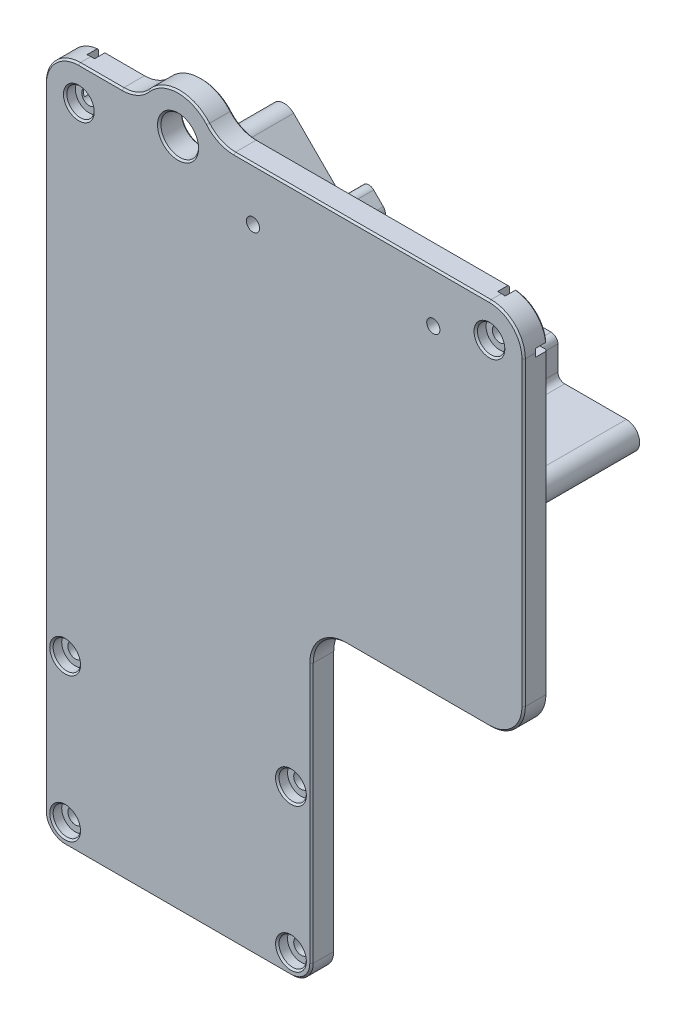
SolidWorks part; units mm, degrees
material "Petg 30% Infill"
ref_plane "Front Plane" through (0, 0, 0) normal (0, 0, 1) x (1, 0, 0)
ref_plane "Top Plane" through (0, 0, 0) normal (0, 1, 0) x (1, 0, 0)
ref_plane "Right Plane" through (0, 0, 0) normal (1, 0, 0) x (0, 0, -1)
sketch "Sketch1" plane through (0, 0, 0) normal (0, 0, 1) x (1, 0, 0)
  line L1 (-29, 200) -> (-16.3172, 200)
  line L2 (-39, 190) -> (-39, 6)
  line L3 (-33, 0) -> (33, 0)
  line L4 (39, 82) -> (39, 6)
  line L5 (101, 190) -> (101, 102)
  line L6 (91, 92) -> (49, 92)
  line L10 (16.3172, 200) -> (91, 200)
  arc A2 (-29, 200) -> (-39, 190) centre (-29, 190) ccw
  arc A5 (49, 92) -> (39, 82) centre (49, 82) ccw
  arc A6 (101, 102) -> (91, 92) centre (91, 102) cw
  arc A7 (91, 200) -> (101, 190) centre (91, 190) cw
  arc A19 (-8.7278, 203.4884) -> (-16.3172, 200) centre (-16.3172, 210) cw
  circle A20 centre (0, 196) radius 5.5
  arc A21 (8.7278, 203.4884) -> (-8.7278, 203.4884) centre (0, 196) ccw
  arc A22 (8.7278, 203.4884) -> (16.3172, 200) centre (16.3172, 210) ccw
  circle A23 centre (-33, 48) radius 2.2
  circle A24 centre (-33, 6) radius 2.2
  circle A25 centre (33, 6) radius 2.2
  circle A26 centre (33, 48) radius 2.2
  arc A27 (-39, 6) -> (-33, 0) centre (-33, 6) ccw
  arc A28 (33, 0) -> (39, 6) centre (33, 6) ccw
  point P4 (0, 0)
  point P70 (10.7819, 200)
  point P80 (-39, 0)
  point P83 (39, 0)
  dimension "D3" = 10
  dimension "D5" = 11
  dimension "D6" = 42
  dimension "D7" = 66
  dimension "D8" = 39
  dimension "D9" = 10
  dimension "D10" = 6
  dimension "D13" = 4.4
  dimension "D1" = 78
  dimension "D2" = 200
  dimension "D4" = 140
  dimension "D12" = 108
  dimension "D14" = 4
extrude "Boss-Extrude1" add sketch "Sketch1" along normal blind 7
sketch "Sketch4" plane through (0, 0, 0) normal (0, 0, -1) x (-1, 0, 0)
  circle A0 centre (29, 190) radius 2.15
  circle A1 centre (-91, 190) radius 2.15
  arc A2 (-91, 200) -> (-101, 190) centre (-91, 190) ccw construction
  dimension "D1" = 4.3
extrude "Cut-Extrude4" cut sketch "Sketch4" against normal up to surface (7 mm away) up to face at (25.25, 123.1865, 7)
sketch "Sketch3" plane through (0, 0, 0) normal (0, 0, -1) x (-1, 0, 0)
  circle A0 centre (-33, 48) radius 4
  circle A1 centre (-33, 6) radius 4
  circle A3 centre (33, 6) radius 4
  circle A4 centre (33, 48) radius 4
  circle A5 centre (-33, 6) radius 2.2 construction
  circle A6 centre (-33, 48) radius 2.2 construction
  circle A7 centre (33, 48) radius 2.2 construction
  circle A8 centre (33, 6) radius 2.2 construction
  circle A9 centre (29, 190) radius 4
  circle A10 centre (-91, 190) radius 4
  dimension "D1" = 8
extrude "countersinks" cut sketch "Sketch3" along normal blind 3 and the other way through all from surface starting at face at (-31.15, 190, 7)
sketch "Sketch7" plane through (0, 0, 0) normal (0, 0, -1) x (-1, 0, 0)
  line L1 (-4.4745, 203.75) -> (-8.9489, 196)
  line L2 (-8.9489, 196) -> (-4.4745, 188.25)
  line L3 (-4.4745, 188.25) -> (4.4745, 188.25)
  line L4 (4.4745, 188.25) -> (8.9489, 196)
  line L5 (8.9489, 196) -> (4.4745, 203.75)
  line L6 (4.4745, 203.75) -> (-4.4745, 203.75)
  circle A0 centre (0, 196) radius 7.75 construction
  arc A1 (8.7278, 203.4884) -> (-8.7278, 203.4884) centre (0, 196) ccw construction
  dimension "D1" = 15.5
extrude "Cut-Extrude7" [suppressed] cut sketch "Sketch7" along normal blind 5.5 from surface starting at face at (87, 190, 7)
chamfer "Chamfer1" distance 0.5 angle 45 46 edges at (35.2, 48, 0) (-30.8, 6, 0) (53.6586, 200, 0) (12.1408, 200.9138, 0) (0, 207.5, 0) (-12.1408, 200.9138, 0) (-22.6586, 200, 0) (-36.0711, 197.0711, 0) (-39, 98, 0) (-37.2426, 1.7574, 0) (0, 0, 0) (37.2426, 1.7574, 0) (39, 44, 0) (41.9289, 89.0711, 0) (70, 92, 0) (98.0711, 94.9289, 0) (101, 146, 0) (98.0711, 197.0711, 0) (-30.8, 48, 0) (35.2, 6, 0) (5.5, 196, 7) (101, 146, 7) (98.0711, 94.9289, 7) (70, 92, 7) (41.9289, 89.0711, 7) (39, 44, 7) (37.2426, 1.7574, 7) (0, 0, 7) (-37.2426, 1.7574, 7) (-39, 98, 7) (-36.0711, 197.0711, 7) (-22.6586, 200, 7) (-12.1408, 200.9138, 7) (0, 207.5, 7) (12.1408, 200.9138, 7) (53.6586, 200, 7) (98.0711, 197.0711, 7) (88.85, 190, 0) (-31.15, 190, 0) (87, 190, 7) (-33, 190, 7) (-37, 48, 7) (-37, 6, 7) (29, 6, 7) (29, 48, 7) (5.5, 196, 0)
sketch "Sketch8" [suppressed] plane through (-39, 0, 0) normal (-1, 0, 0) x (0, 0, 1)
  line L0 (6.5, 190) -> (0.5, 190) construction
  circle A0 centre (3.5, 175) radius 1.85
  circle A1 centre (3.5, 160) radius 1.85
  circle A2 centre (3.5, 145) radius 1.85
  circle A3 centre (3.5, 130) radius 1.85
  circle A4 centre (3.5, 115) radius 1.85
  circle A5 centre (3.5, 100) radius 1.85
  circle A6 centre (3.5, 85) radius 1.85
  circle A7 centre (3.5, 70) radius 1.85
  circle A8 centre (3.5, 55) radius 1.85
  circle A9 centre (3.5, 40) radius 1.85
  circle A10 centre (3.5, 25) radius 1.85
  point P5 (3.5, 190)
  dimension "D1" = 3.7
  dimension "D2" = 15
  dimension "D4" = 15
  dimension "D3" = 11
extrude "Cut-Extrude8" [suppressed] cut sketch "Sketch8" against normal blind 20
sketch "Sketch9" [suppressed] plane through (39, 0, 0) normal (1, 0, 0) x (0, 0, -1)
  line L0 (-6.5, 82) -> (-0.5, 82) construction
  circle A0 centre (-3.5, 67) radius 1.85
  circle A1 centre (-3.5, 52) radius 1.85
  circle A2 centre (-3.5, 37) radius 1.85
  circle A3 centre (-3.5, 22) radius 1.85
  circle A4 centre (-3.5, 7) radius 1.85
  point P4 (-3.5, 82)
  dimension "D2" = 3.7
  dimension "D1" = 15
  dimension "D3" = 5
extrude "Cut-Extrude9" [suppressed] cut sketch "Sketch9" against normal blind 20
sketch "Sketch12" [suppressed] plane through (0, 0, 0) normal (0, 0, -1) x (-1, 0, 0)
  line L0 (39, 190) -> (39, 6) construction
  line L1 (-76.3286, 190) -> (-11.8357, 190)
  line L2 (-91, 175.3286) -> (-91, 107)
  line L3 (-86, 102) -> (24, 102)
  line L4 (29, 175.3286) -> (29, 107)
  line L7 (-5.9178, 183.75) -> (5.9178, 183.75)
  line L11 (-91, 200) -> (-16.3172, 200) construction
  line L12 (-101, 102) -> (-101, 190) construction
  line L13 (-49, 92) -> (-91, 92) construction
  line L14 (-7.6499, 184.75) -> (-10.1036, 189)
  line L15 (-4.7631, 187.75) -> (-9.5263, 196) construction
  line L16 (11.8357, 190) -> (16.661, 190)
  line L17 (9.5263, 196) -> (4.7631, 187.75) construction
  line L18 (4.7631, 187.75) -> (-4.7631, 187.75) construction
  line L20 (7.6499, 184.75) -> (10.1036, 189)
  arc A19 (-87.6129, 180.0613) -> (-81.0613, 186.6129) centre (-91, 190) ccw
  arc A21 (18.6353, 188.32) -> (25.6129, 180.0613) centre (29, 190) ccw
  arc A22 (-87.6129, 180.0613) -> (-91, 175.3286) centre (-86, 175.3286) ccw
  circle A23 centre (-91, 190) radius 4.5 construction
  circle A24 centre (29, 190) radius 4.5 construction
  arc A25 (-91, 107) -> (-86, 102) centre (-86, 107) ccw
  arc A26 (24, 102) -> (29, 107) centre (24, 107) ccw
  arc A27 (25.6129, 180.0613) -> (29, 175.3286) centre (24, 175.3286) cw
  arc A28 (-81.0613, 186.6129) -> (-76.3286, 190) centre (-76.3286, 185) cw
  arc A29 (-10.1036, 189) -> (-11.8357, 190) centre (-11.8357, 188) ccw
  arc A30 (-7.6499, 184.75) -> (-5.9178, 183.75) centre (-5.9178, 185.75) ccw
  arc A31 (10.1036, 189) -> (11.8357, 190) centre (11.8357, 188) cw
  arc A32 (16.661, 190) -> (18.6353, 188.32) centre (16.661, 188) cw
  arc A33 (5.9178, 183.75) -> (7.6499, 184.75) centre (5.9178, 185.75) ccw
  point P26 (10.681, 190)
  dimension "D4" = 2
  dimension "D5" = 4
  dimension "D10" = 6
  dimension "D11" = 6
  dimension "D2" = 5
  dimension "D3" = 5
  dimension "D6" = 10
  dimension "D7" = 10
  dimension "D8" = 10
  dimension "D9" = 10
  dimension "D12" = 4
  dimension "D13" = 4
extrude "Cut-Extrude10" [suppressed] cut sketch "Sketch12" against normal blind 10
sketch "Sketch14" [suppressed] plane through (0, 0, 0) normal (0, 0, -1) x (-1, 0, 0)
  line L0 (-33, 0.5) -> (33, 0.5) construction
  line L1 (-22.5, 104.5) -> (22.5, 104.5)
  line L2 (-26.5, 100.5) -> (-26.5, 58.5)
  line L3 (-22.5, 54.5) -> (22.5, 54.5)
  line L4 (26.5, 100.5) -> (26.5, 58.5)
  line L5 (-22.5, 41.5) -> (22.5, 41.5)
  line L6 (-26.5, 37.5) -> (-26.5, 16.5)
  line L7 (-22.5, 12.5) -> (22.5, 12.5)
  line L8 (26.5, 37.5) -> (26.5, 16.5)
  arc A0 (-26.5, 16.5) -> (-22.5, 12.5) centre (-22.5, 16.5) ccw
  arc A1 (22.5, 12.5) -> (26.5, 16.5) centre (22.5, 16.5) ccw
  arc A2 (22.5, 41.5) -> (26.5, 37.5) centre (22.5, 37.5) cw
  arc A3 (-22.5, 41.5) -> (-26.5, 37.5) centre (-22.5, 37.5) ccw
  arc A4 (-26.5, 58.5) -> (-22.5, 54.5) centre (-22.5, 58.5) ccw
  arc A5 (22.5, 54.5) -> (26.5, 58.5) centre (22.5, 58.5) ccw
  arc A6 (22.5, 104.5) -> (26.5, 100.5) centre (22.5, 100.5) cw
  arc A7 (-22.5, 104.5) -> (-26.5, 100.5) centre (-22.5, 100.5) ccw
  circle A9 centre (33, 6) radius 4.5 construction
  circle A10 centre (-33, 48) radius 4.5 construction
  circle A15 centre (33, 48) radius 4.5 construction
  point P24 (0, 54.5)
  point P25 (0, 41.5)
  point P34 (0, 0.5)
  point P35 (0, 12.5)
  dimension "D1" = 4
  dimension "D4" = 2
  dimension "D5" = 50
  dimension "D2" = 2
  dimension "D6" = 2
  dimension "D3" = 2
extrude "lightweiting" [suppressed] cut sketch "Sketch14" against normal up to surface (10 mm away) contours L2 A4 L3 A5 L4 A6 L1 A7 | L6 A0 L7 A1 L8 A2 L5 A3 up to face at (-6, 196, 7)
chamfer "Chamfer2" [suppressed] distance 0.5 angle 45
sketch "Sketch15" plane through (0, 0, 7) normal (0, 0, 1) x (1, 0, 0)
  circle A2 centre (21.8994, 184.6949) radius 1.925
  circle A3 centre (74.5928, 185.3298) radius 1.925
  circle A5 centre (21.8994, 184.6949) radius 2.0076 construction
  circle A6 centre (74.5928, 185.3298) radius 2.0076 construction
  dimension "D6" = 3.85
sketch "Sketch16" plane through (0, 0, 0) normal (0, 0, -1) x (-1, 0, 0)
  line L0 (-69.01, 145.9337) -> (-87.01, 145.9337)
  line L1 (-61.01, 127.0337) -> (-65.01, 127.0337)
  line L2 (-59.01, 129.0337) -> (-59.01, 155.0337)
  line L3 (-61.01, 157.0337) -> (-65.01, 157.0337)
  line L4 (-67.01, 129.0337) -> (-67.01, 136.1337)
  line L5 (-69.01, 138.1337) -> (-87.01, 138.1337)
  line L6 (-67.01, 147.9337) -> (-67.01, 155.0337)
  line L7 (2.3834, 143.0424) -> (-16.0014, 161.4271)
  line L8 (-16.0014, 164.2556) -> (-13.1729, 167.084)
  line L9 (-10.3445, 167.084) -> (-5.324, 162.0635)
  line L10 (-2.4956, 162.0635) -> (10.2323, 174.7915)
  line L13 (15.7477, 169.276) -> (3.0198, 156.5481)
  line L14 (3.0198, 153.7197) -> (8.0403, 148.6992)
  line L15 (8.0403, 145.8708) -> (5.2118, 143.0424)
  line L16 (12.99, 172.0337) -> (9.6605, 168.7043) construction
  line L17 (39, 190) -> (39, 6) construction
  arc A0 (-87.01, 145.9337) -> (-87.01, 138.1337) centre (-87.01, 142.0337) ccw
  circle A1 centre (-87.01, 142.0337) radius 1.9
  arc A2 (-69.01, 145.9337) -> (-67.01, 147.9337) centre (-69.01, 147.9337) ccw
  arc A3 (-65.01, 157.0337) -> (-67.01, 155.0337) centre (-65.01, 155.0337) ccw
  arc A4 (-59.01, 155.0337) -> (-61.01, 157.0337) centre (-61.01, 155.0337) ccw
  arc A5 (-61.01, 127.0337) -> (-59.01, 129.0337) centre (-61.01, 129.0337) ccw
  arc A6 (-65.01, 127.0337) -> (-67.01, 129.0337) centre (-65.01, 129.0337) cw
  arc A7 (-69.01, 138.1337) -> (-67.01, 136.1337) centre (-69.01, 136.1337) cw
  circle A8 centre (-87.01, 142.0337) radius 2.15 construction
  circle A9 centre (12.99, 172.0337) radius 1.9
  arc A10 (15.7477, 169.276) -> (10.2323, 174.7915) centre (12.99, 172.0337) ccw
  circle A11 centre (12.99, 172.0337) radius 2.15 construction
  arc A12 (-5.324, 162.0635) -> (-2.4956, 162.0635) centre (-3.9098, 163.4778) ccw
  arc A13 (3.0198, 156.5481) -> (3.0198, 153.7197) centre (4.434, 155.1339) ccw
  arc A14 (8.0403, 148.6992) -> (8.0403, 145.8708) centre (6.6261, 147.285) cw
  arc A15 (2.3834, 143.0424) -> (5.2118, 143.0424) centre (3.7976, 144.4566) ccw
  arc A16 (-16.0014, 161.4271) -> (-16.0014, 164.2556) centre (-14.5871, 162.8414) cw
  arc A17 (-13.1729, 167.084) -> (-10.3445, 167.084) centre (-11.7587, 165.6698) cw
  point P10 (-59.01, 142.0337)
  point P13 (-67.01, 145.9337)
  point P39 (10.3333, 169.8822)
  dimension "D1" = 3.8
  dimension "D2" = 2
  dimension "D3" = 2
  dimension "D7" = 3.8
  dimension "D8" = 2
  dimension "D4" = 30
  dimension "D5" = 8
  dimension "D6" = 20
  dimension "D9" = 45
extrude "Boss-Extrude3" add sketch "Sketch16" along normal blind 37
sketch "Sketch17" plane through (0, 0, 0) normal (0, 0, -1) x (-1, 0, 0)
  circle A0 centre (29, 190) radius 10
  arc A1 (39, 190) -> (29, 200) centre (29, 190) ccw construction
extrude "Cut-Extrude11" cut sketch "Sketch17" against normal blind 0.1
sketch "Sketch18" [suppressed] plane through (0, 0, 0) normal (0, 0, -1) x (-1, 0, 0)
  line L0 (0, 22) -> (0, 32) construction
  line L1 (-33, 48) -> (33, 6) construction
  circle A0 centre (0, 32) radius 1.9
  circle A1 centre (0, 22) radius 1.9
  circle A2 centre (-33, 48) radius 4.5 construction
  circle A3 centre (33, 6) radius 4.5 construction
  point P12 (0, 27)
  point P13 (0, 27)
  dimension "D2" = 3.8
  dimension "D1" = 10
extrude "Cut-Extrude12" [suppressed] cut sketch "Sketch18" against normal through all
sketch "Sketch21" plane through (0, 0, 0) normal (0, 0, -1) x (-1, 0, 0)
  line L0 (29, 202) -> (29, 190) construction
  line L1 (29, 190) -> (41, 190) construction
  line L2 (27.9, 201.9495) -> (27.9, 191.8473)
  line L3 (30.8473, 188.9) -> (40.9495, 188.9)
  line L4 (30.1, 201.9495) -> (30.1, 191.8473)
  line L5 (30.8473, 191.1) -> (40.9495, 191.1)
  line L6 (29, 204.8399) -> (29, 190) construction
  line L7 (27.9, 204.8399) -> (27.9, 188.9) construction
  line L8 (30.1, 204.8399) -> (30.1, 191.1) construction
  line L9 (27.9, 188.9) -> (44.9472, 188.9) construction
  line L10 (30.1, 191.1) -> (44.9472, 191.1) construction
  line L11 (29, 190) -> (44.9472, 190) construction
  line L12 (-101, 166.3023) -> (39, 166.3023) construction
  line L13 (-101, 102) -> (-101, 190) construction
  line L14 (39, 190) -> (39, 6) construction
  line L15 (-31, 233.9591) -> (-31, 186.4479) construction
  line L16 (-91, 190) -> (-103, 190) construction
  line L17 (-91, 202) -> (-91, 190) construction
  line L18 (-92.8473, 191.1) -> (-102.9495, 191.1)
  line L19 (-92.1, 201.9495) -> (-92.1, 191.8473)
  line L20 (-92.8473, 188.9) -> (-102.9495, 188.9)
  line L21 (-89.9, 201.9495) -> (-89.9, 191.8473)
  arc A0 (30.8473, 188.9) -> (30.8473, 191.1) centre (29, 190) ccw
  arc A1 (30.1, 201.9495) -> (27.9, 201.9495) centre (29, 190) ccw
  arc A2 (39, 190) -> (29, 200) centre (29, 190) ccw construction
  circle A3 centre (29, 190) radius 2.15 construction
  arc A4 (40.9495, 188.9) -> (40.9495, 191.1) centre (29, 190) ccw
  arc A5 (30.1, 191.8473) -> (27.9, 191.8473) centre (29, 190) ccw
  arc A6 (-92.1, 191.8473) -> (-89.9, 191.8473) centre (-91, 190) cw
  arc A7 (-102.9495, 188.9) -> (-102.9495, 191.1) centre (-91, 190) cw
  arc A8 (-92.1, 201.9495) -> (-89.9, 201.9495) centre (-91, 190) cw
  arc A9 (-92.8473, 188.9) -> (-92.8473, 191.1) centre (-91, 190) cw
  point P33 (-31, 166.3023)
  dimension "D1" = 2
  dimension "D2" = 1.1
  dimension "D3" = 1.1
extrude "Cut-Extrude14" cut sketch "Sketch21" against normal blind 3.5
chamfer "Chamfer4" distance 2 angle 45 28 edges at (16.5871, 162.8414, 0) (6.809, 152.2348, 0) (14.5871, 165.6698, 0) (-3.7976, 142.4566, 0) (11.7587, 167.6698, 0) (-6.6261, 144.4566, 0) (7.8343, 164.5738, 0) (-8.6261, 147.285, 0) (3.9098, 161.4778, 0) (-5.53, 151.2095, 0) (-3.8683, 168.4275, 0) (-2.434, 155.1339, 0) (-15.7477, 174.7915, 0) (-9.3838, 162.9121, 0) (90.91, 142.0337, 0) (78.01, 138.1337, 0) (78.01, 145.9337, 0) (67.5958, 137.548, 0) (67.5958, 146.5195, 0) (67.01, 132.5837, 0) (67.01, 151.4837, 0) (66.4242, 127.6195, 0) (66.4242, 156.448, 0) (63.01, 127.0337, 0) (63.01, 157.0337, 0) (59.5958, 127.6195, 0) (59.5958, 156.448, 0) (59.01, 142.0337, 0)
extrude "Cut-Extrude15" cut sketch "Sketch15" against normal up to surface (7 mm away) up to face at (0.0973, 158.9464, 0)
